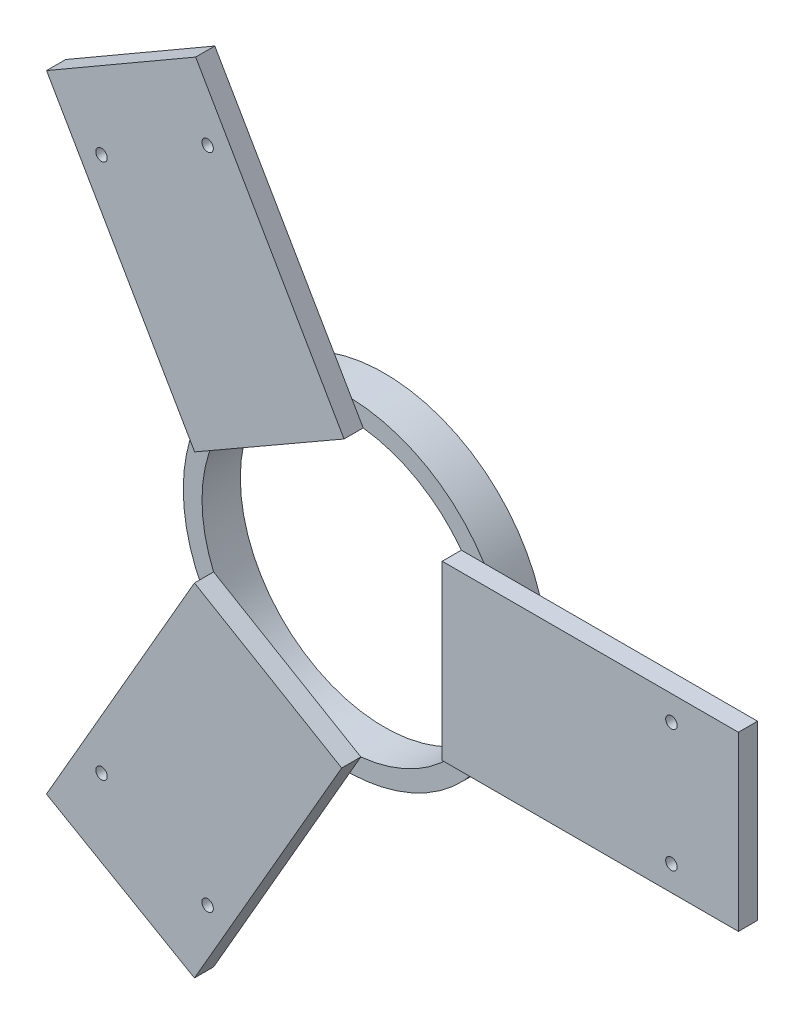
SolidWorks part; units mm, degrees
ref_plane "Front Plane" through (0, 0, 0) normal (0, 0, 1) x (1, 0, 0)
ref_plane "Top Plane" through (0, 0, 0) normal (0, 1, 0) x (1, 0, 0)
ref_plane "Right Plane" through (0, 0, 0) normal (1, 0, 0) x (0, 0, -1)
sketch "Sketch1" plane through (0, 0, 0) normal (0, 0, 1) x (1, 0, 0)
  circle A0 centre (300, 300) radius 85
extrude "Boss-Extrude1" add sketch "Sketch1" along normal blind 20
sketch "Sketch2" plane through (0, 0, 20) normal (0, 0, 1) x (1, 0, 0)
  circle A0 centre (300, 300) radius 75.2
extrude "Cut-Extrude1" cut sketch "Sketch2" against normal blind 40
ref_plane "Plane1" through (0, 0, 20) normal (0, 0, 1) x (1, 0, 0)
sketch "Sketch3" plane through (0, 0, 20) normal (0, 0, 1) x (1, 0, 0)
  line L0 (360.16, 254.88) -> (515, 254.88)
  line L1 (515, 254.88) -> (515, 345)
  line L2 (515, 345) -> (360.2498, 345)
  line L3 (360.2498, 345) -> (360.16, 254.88)
  circle A0 centre (300, 300) radius 75.2 construction
extrude "Boss-Extrude2" add sketch "Sketch3" along normal blind 10
sketch "Sketch4" plane through (0, 0, 30) normal (0, 0, 1) x (1, 0, 0)
  circle A0 centre (480, 268) radius 3
extrude "Cut-Extrude2" cut sketch "Sketch4" against normal blind 50
sketch "Sketch5" plane through (0, 0, 30) normal (0, 0, 1) x (1, 0, 0)
  circle A0 centre (480, 332) radius 3
extrude "Cut-Extrude3" cut sketch "Sketch5" against normal blind 50
ref_plane "Plane2" through (0, 0, 20) normal (0, 0, 1) x (1, 0, 0)
sketch "Sketch6" plane through (0, 0, 20) normal (0, 0, 1) x (1, 0, 0)
  line L0 (308.9951, 374.6601) -> (231.4711, 508.6955)
  line L1 (231.4711, 508.6955) -> (153.5638, 463.6351)
  line L2 (153.5638, 463.6351) -> (230.9631, 329.8152)
  line L3 (230.9631, 329.8152) -> (308.9951, 374.6601)
  arc A0 (360.2498, 345) -> (360.16, 254.88) centre (300, 300) ccw construction
extrude "Boss-Extrude3" add sketch "Sketch6" along normal blind 10
sketch "Sketch7" plane through (0, 0, 30) normal (0, 0, 1) x (1, 0, 0)
  circle A0 centre (237.7128, 471.8846) radius 3
extrude "Cut-Extrude4" cut sketch "Sketch7" against normal blind 50
sketch "Sketch8" plane through (0, 0, 30) normal (0, 0, 1) x (1, 0, 0)
  circle A0 centre (182.2872, 439.8846) radius 3
extrude "Cut-Extrude5" cut sketch "Sketch8" against normal blind 50
ref_plane "Plane3" through (0, 0, 20) normal (0, 0, 1) x (1, 0, 0)
sketch "Sketch9" plane through (0, 0, 20) normal (0, 0, 1) x (1, 0, 0)
  line L0 (230.8449, 270.4599) -> (153.5289, 136.3045)
  line L1 (153.5289, 136.3045) -> (230.8449, 91.7459)
  line L2 (230.8449, 91.7459) -> (307.7575, 225.2012)
  line L3 (307.7575, 225.2012) -> (230.8449, 270.4599)
  arc A0 (230.9631, 329.8152) -> (360.16, 254.88) centre (300, 300) ccw construction
extrude "Boss-Extrude4" add sketch "Sketch9" along normal blind 10
sketch "Sketch10" plane through (0, 0, 30) normal (0, 0, 1) x (1, 0, 0)
  circle A0 centre (182.2872, 160.1154) radius 3
extrude "Cut-Extrude6" cut sketch "Sketch10" against normal blind 50
sketch "Sketch11" plane through (0, 0, 30) normal (0, 0, 1) x (1, 0, 0)
  circle A0 centre (237.7128, 128.1154) radius 3
extrude "Cut-Extrude7" cut sketch "Sketch11" against normal blind 50
